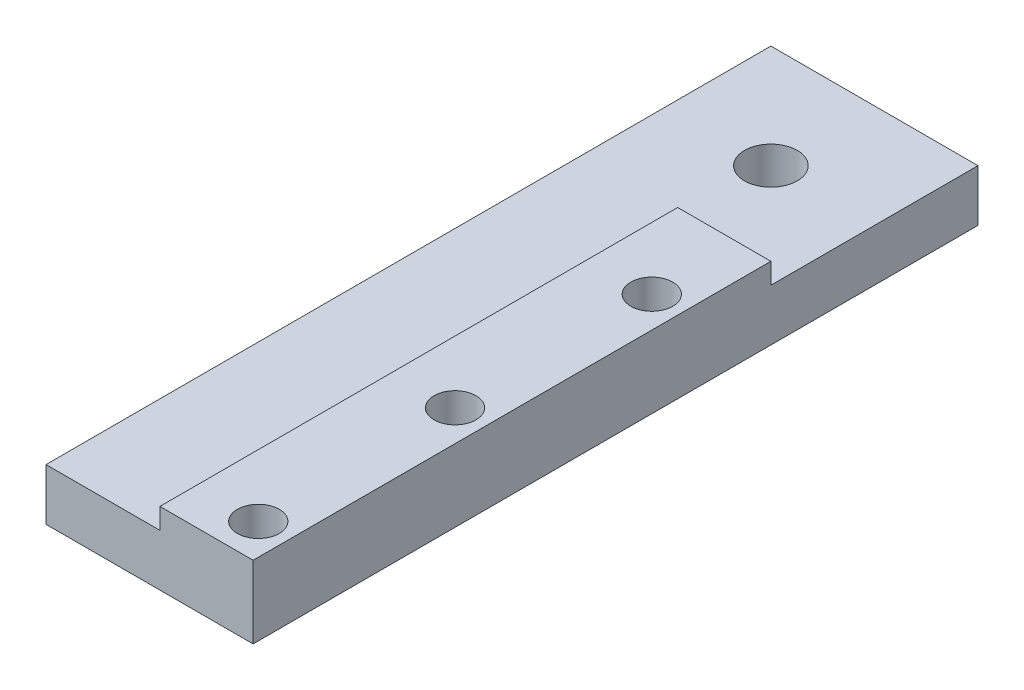
SolidWorks part; units mm, degrees
ref_plane "Front Plane" through (0, 0, 0) normal (0, 0, 1) x (1, 0, 0)
ref_plane "Top Plane" through (0, 0, 0) normal (0, 1, 0) x (1, 0, 0)
ref_plane "Right Plane" through (0, 0, 0) normal (1, 0, 0) x (0, 0, -1)
sketch "Sketch1" plane through (0, 0, 0) normal (0, 1, 0) x (1, 0, 0)
  line L0 (6, 22.4994) -> (0, 22.4994) construction
  line L1 (0, 0) -> (9, 0)
  line L2 (0, 0) -> (0, 50)
  line L3 (0, 50) -> (9, 50)
  line L4 (9, 0) -> (9, 50)
  line L6 (9, 50) -> (-11, 50)
  line L7 (9, 50) -> (9, 70)
  line L8 (9, 70) -> (-11, 70)
  line L9 (-11, 50) -> (-11, 70)
  line L10 (0, 0) -> (-11, 0)
  line L11 (0, 0) -> (0, 50)
  line L12 (0, 50) -> (-11, 50)
  line L13 (-11, 0) -> (-11, 50)
  circle A0 centre (6, 3.4994) radius 2.025
  circle A1 centre (6, 22.4994) radius 2.025
  circle A2 centre (6, 41.4994) radius 2.025
  circle A3 centre (-1, 60) radius 2.55
  dimension "D2" = 19
  dimension "D4" = 4.05
  dimension "D5" = 4.05
  dimension "D10" = 5.1
  dimension "D1" = 9
  dimension "D3" = 50
  dimension "D6" = 3
  dimension "D7" = 3
  dimension "D8" = 20
  dimension "D9" = 20
extrude "Boss-Extrude1" add sketch "Sketch1" against normal blind 5 contours L9 L6 L3 L7 L8 A3 | A1 L2 L1 L4 L3 A0 A2 | L13 L10 L2 L11 L6 region at (4.3591, 0, -25.2349) region at (-5.5, 0, -25) region at (-5.5, 0, -50.2828)
extrude "Boss-Extrude2" add sketch "Sketch1<3>" along normal blind 2 contours A1 L2 L1 L4 L3 L11 A0 A2 region at (4.3591, 0, -25.2349)
sketch "Sketch1<3>" plane through (0, 0, 0) normal (0, 1, 0) x (1, 0, 0) same geometry as "Sketch1"
